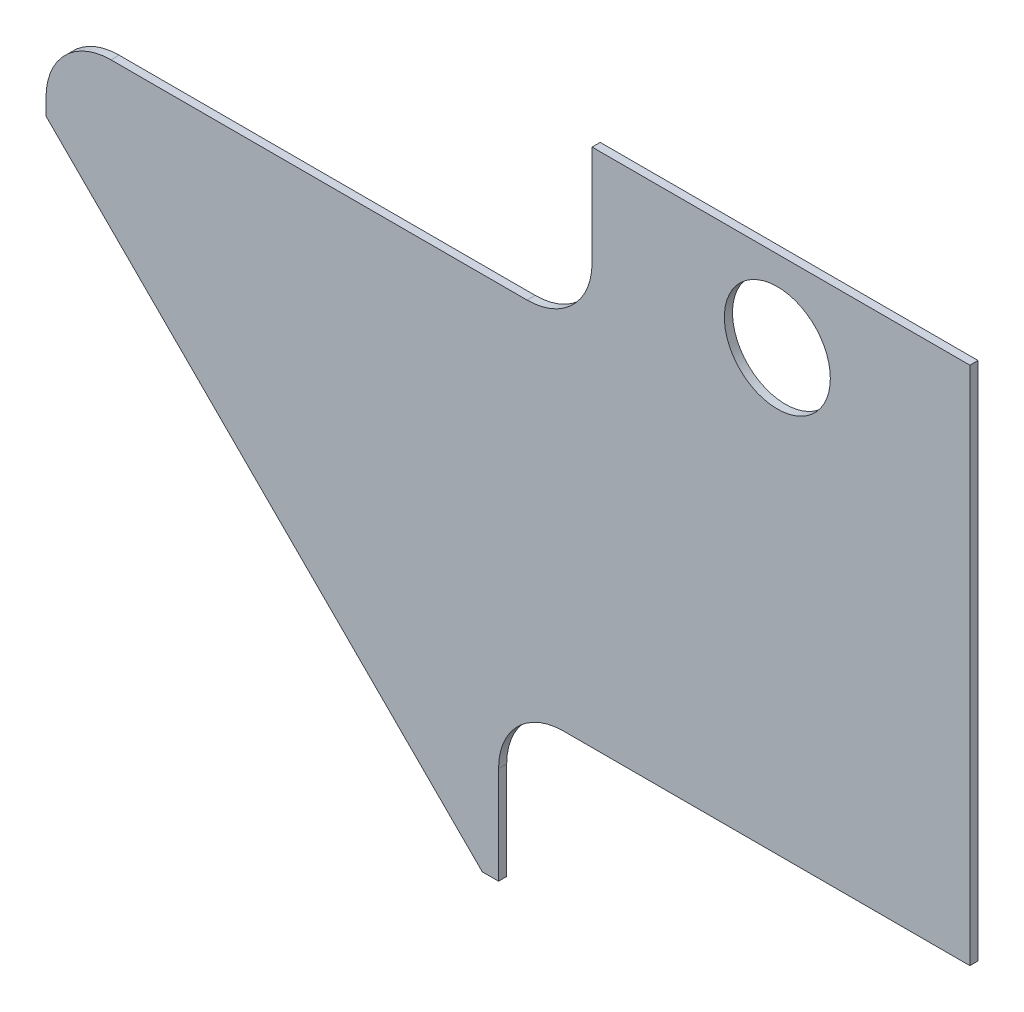
SolidWorks part; units mm, degrees
ref_plane "Front Plane" through (0, 0, 0) normal (0, 0, 1) x (1, 0, 0)
ref_plane "Top Plane" through (0, 0, 0) normal (0, 1, 0) x (1, 0, 0)
ref_plane "Right Plane" through (0, 0, 0) normal (1, 0, 0) x (0, 0, -1)
sketch "Sketch1" plane through (0, 0, 0) normal (0, 0, 1) x (1, 0, 0)
  line L0 (-138.2594, 48.9915) -> (32.2106, -121.4785)
  line L1 (32.2106, -121.4785) -> (222.7106, -121.4785)
  line L2 (-138.2594, 145.2215) -> (-138.2594, 48.9915)
  line L3 (-138.2594, 145.2215) -> (222.7106, 145.2215)
  line L4 (222.7106, -121.4785) -> (222.7106, 145.2215)
  circle A0 centre (147.4906, 113.4715) radius 20.701
  circle A2 centre (147.4906, 113.4715) radius 69.85 construction
  circle A3 centre (147.4906, 113.4715) radius 285.75 construction
  point P0 (0, 0)
  point P2 (147.4906, 113.4715)
  dimension "D4" = 234.95
  dimension "D1" = 45
  dimension "D2" = 266.7
  dimension "D5" = 247.65
extrude "Boss-Extrude1" add sketch "Sketch1" along normal blind 3.175
sketch "Sketch2" plane through (0, 0, 3.175) normal (0, 0, 1) x (1, 0, 0)
  line L0 (222.7106, 145.2215) -> (-138.2594, 145.2215) construction
  line L1 (222.7106, -121.4785) -> (38.5606, -121.4785)
  line L2 (222.7106, -121.4785) -> (222.7106, -57.9785)
  line L3 (222.7106, -57.9785) -> (38.5606, -57.9785)
  line L4 (38.5606, -121.4785) -> (38.5606, -57.9785)
  line L5 (75.1006, 145.2215) -> (-138.2594, 145.2215)
  line L6 (75.1006, 145.2215) -> (75.1006, 80.7415)
  line L7 (75.1006, 80.7415) -> (-138.2594, 80.7415)
  line L8 (-138.2594, 145.2215) -> (-138.2594, 80.7415)
  line L9 (-138.2594, 145.2215) -> (-138.2594, 48.9915) construction
  dimension "D1" = 31.75
  dimension "D2" = 6.35
extrude "Cut-Extrude1" cut sketch "Sketch2" against normal through all
fillet "Fillet1" radius 25.4 1 edges at (75.1006, 80.7415, 1.5875)
fillet "Fillet2" radius 25.4 2 edges at (38.5606, -57.9785, 1.5875) (-138.2594, 80.7415, 1.5875)
